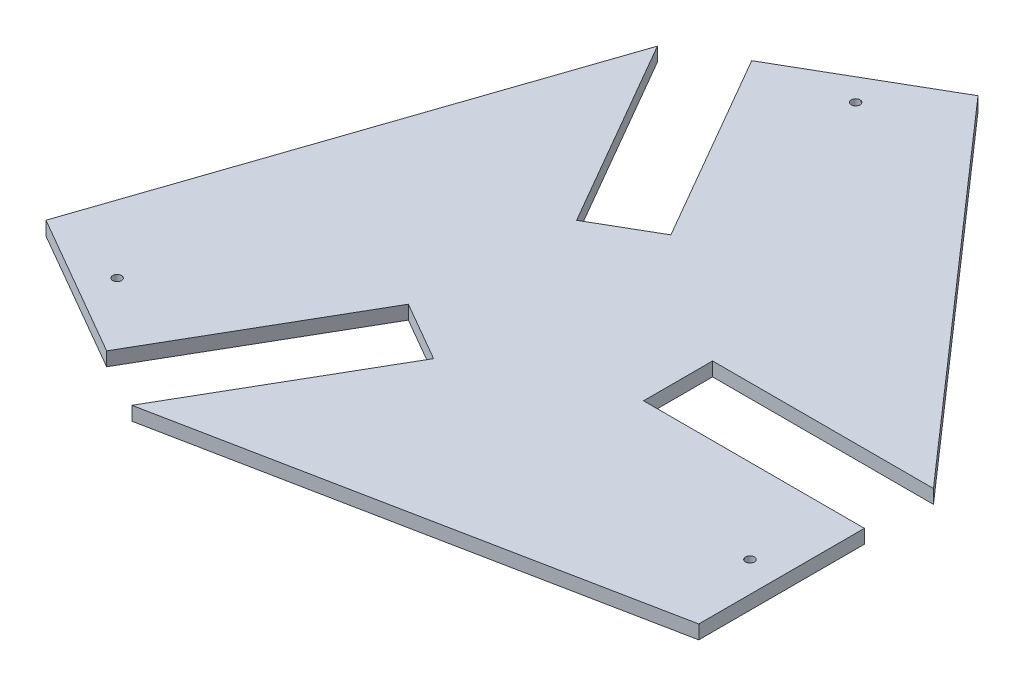
SolidWorks part; units mm, degrees
ref_plane "Front Plane" through (0, 0, 0) normal (0, 0, 1) x (1, 0, 0)
ref_plane "Top Plane" through (0, 0, 0) normal (0, 1, 0) x (1, 0, 0)
ref_plane "Right Plane" through (0, 0, 0) normal (1, 0, 0) x (0, 0, -1)
sketch "Sketch1" plane through (0, 0, 0) normal (0, 1, 0) x (1, 0, 0)
  line L0 (76.2, -47.5615) -> (76.2, 6.4135) construction
  line L1 (76.2, -47.5615) -> (-32.5457, -69.1979)
  line L2 (-43.6543, 62.7844) -> (-79.2895, -42.2104)
  line L5 (-79.2895, -42.2104) -> (-32.5457, -69.1979) construction
  line L6 (76.2, 6.4135) -> (25.4, 6.4135)
  line L7 (25.4, 6.4135) -> (25.4, -9.4615)
  line L8 (25.4, -9.4615) -> (76.2, -9.4615)
  line L9 (76.2, -9.4615) -> (76.2, -47.5615)
  line L10 (3.0895, 89.7719) -> (76.2, 6.4135)
  line L11 (-46.2939, -61.2604) -> (-79.2895, -42.2104)
  line L12 (-20.8939, -17.2663) -> (-46.2939, -61.2604)
  line L13 (-32.5457, -69.1979) -> (-7.1457, -25.2038)
  line L14 (-7.1457, -25.2038) -> (-20.8939, -17.2663)
  line L16 (3.0895, 89.7719) -> (-43.6543, 62.7844) construction
  line L17 (-29.9061, 70.7219) -> (3.0895, 89.7719)
  line L18 (-4.5061, 26.7278) -> (-29.9061, 70.7219)
  line L19 (-43.6543, 62.7844) -> (-18.2543, 18.7903)
  line L20 (-18.2543, 18.7903) -> (-4.5061, 26.7278)
  line L21 (0, 0) -> (-49999.9986, 0) construction
  line L22 (0, 0) -> (-25000, 43301.2702) construction
  line L23 (0, 0) -> (-25000, -43301.2702) construction
  line L24 (25.4, 0) -> (76.2, 0) construction
  line L25 (-12.7, -21.997) -> (-38.1, -65.9911) construction
  line L26 (-12.7, 21.997) -> (-38.1, 65.9911) construction
  line L27 (76.2, 8.001) -> (76.2, 45.974) [skipped]
  line L28 (-31.1709, -69.9916) -> (1.7147, -88.9781) [skipped]
  line L29 (-45.0291, 61.9906) -> (-77.9147, 43.0041) [skipped]
  circle A0 centre (69.2404, -28.829) radius 1.016
  circle A1 centre (0, 0) radius 76.2 construction
  circle A2 centre (-59.5868, -45.5494) radius 1.016
  circle A3 centre (-9.6536, 74.3784) radius 1.016
  dimension "D2" = 15.875
  dimension "D6" = 152.4
  dimension "D13" = 2.032
  dimension "D1" = 120
  dimension "D3" = 50.8
  dimension "D4" = 38.1
  dimension "D5" = 3
  dimension "D7" = 9.4615
  dimension "D9" = 120
  dimension "D10" = 120
  dimension "D11" = 6.9596
  dimension "D12" = 19.3675
  dimension "D8" = 3
  dimension "D14" = 3
extrude "Boss-Extrude2" add sketch "Sketch1" along normal blind 3.175
